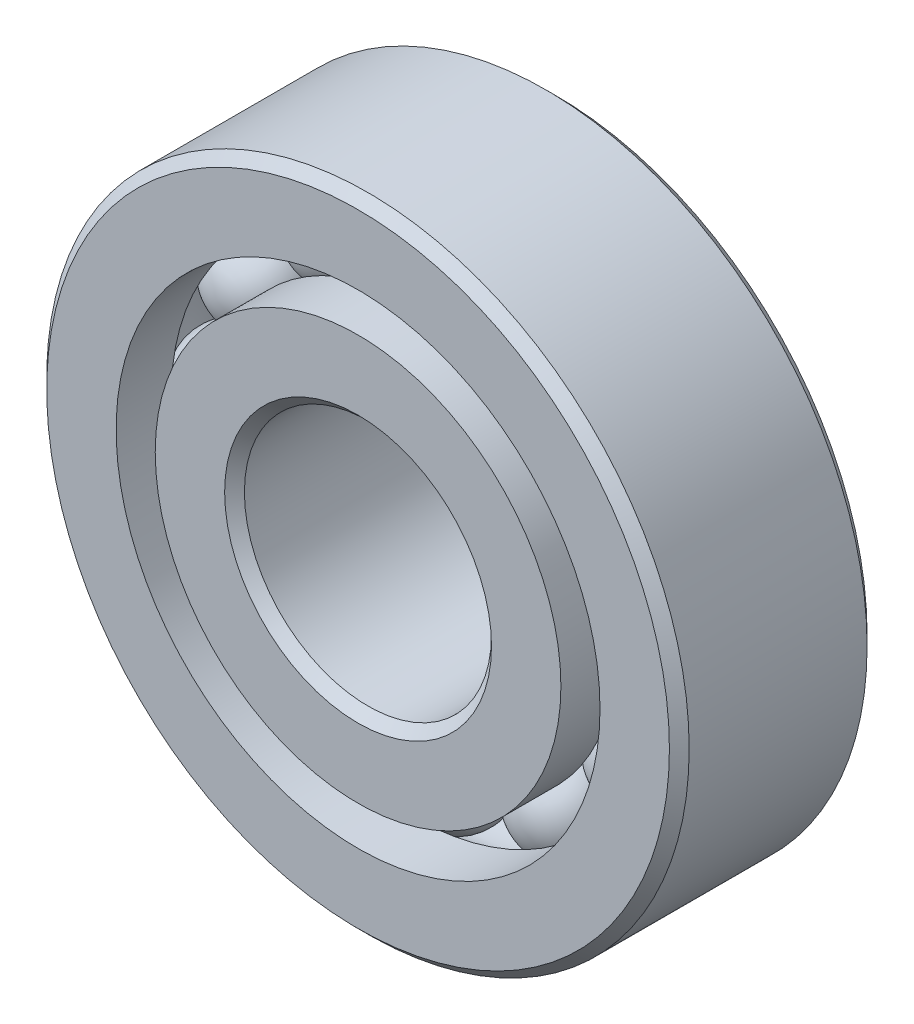
SolidWorks part; units mm, degrees
ref_plane "Front Plane" through (0, 0, 0) normal (0, 0, 1) x (1, 0, 0)
ref_plane "Top Plane" through (0, 0, 0) normal (0, 1, 0) x (1, 0, 0)
ref_plane "Right Plane" through (0, 0, 0) normal (1, 0, 0) x (0, 0, -1)
sketch "Sketch1" plane through (0, 0, 0) normal (1, 0, 0) x (0, 0, -1)
  line L0 (-4, 0) -> (4, 0) construction
  line L1 (0, 13) -> (0, -13) construction
  line L2 (3.6, 13) -> (-3.6, 13)
  line L3 (-3.6, 13) -> (-4, 12.6)
  line L4 (-4, 12.6) -> (-4, 9.7912)
  line L5 (-4, 9.7912) -> (-1.7778, 9.7912)
  line L6 (4, 9.7912) -> (1.7778, 9.7912)
  line L7 (4, 12.6) -> (4, 9.7912)
  line L8 (3.6, 13) -> (4, 12.6)
  line L9 (0, 13) -> (0, 9) construction
  line L10 (0, 9) -> (0, 5) construction
  arc A0 (-1.7778, 9.7912) -> (1.7778, 9.7912) centre (0, 9) cw
  point P14 (0, 5)
  dimension "Width" = 8
  dimension "OD" = 26
  dimension "D1" = 45
  dimension "D2" = 0.4
  dimension "Shaft Dia" = 10
  dimension "D3" = 3.5556
  dimension "D4" = 0.7912
revolve "Revolve1" add sketch "Sketch1" angle 360 about L0
sketch "Sketch3" plane through (0, 0, 0) normal (1, 0, 0) x (0, 0, -1)
  line L0 (-4, 8.2088) -> (-1.7778, 8.2088)
  line L1 (0, 13) -> (0, -13) construction
  line L2 (-4, 12.6) -> (-4, 9.7912) construction
  line L3 (-4, 8.2088) -> (-4, 5.4)
  line L4 (-3.6, 13) -> (-4, 12.6) construction
  line L5 (-4, 5.4) -> (-3.6, 5)
  line L6 (-3.6, 5) -> (3.6, 5)
  line L7 (3.6, 13) -> (3.6, -13) construction
  line L8 (3.6, 5) -> (4, 5.4)
  line L9 (4, -12.6) -> (4, 12.6) construction
  line L10 (4, 5.4) -> (4, 8.2088)
  line L11 (4, 8.2088) -> (1.7778, 8.2088)
  line L13 (3.6, 13) -> (4, 12.6) construction
  arc A0 (1.7778, 9.7912) -> (-1.7778, 9.7912) centre (0, 9) ccw construction
  arc A1 (1.7778, 8.2088) -> (-1.7778, 8.2088) centre (0, 9) cw
revolve "Revolve3" add sketch "Sketch3" angle 360 about L0
sketch "Sketch4" plane through (0, 0, 0) normal (1, 0, 0) x (0, 0, -1)
  line L0 (-1.9459, 9) -> (1.9459, 9)
  arc A2 (-1.9459, 9) -> (1.9459, 9) centre (0, 9) cw
  arc A3 (1.7778, 9.7912) -> (-1.7778, 9.7912) centre (0, 9) ccw construction
revolve "Revolve4" add sketch "Sketch4" angle 360 about L0
ref_axis "Axis1" through (0, 0, -4) along (0, 0, 1)
pattern_circular "CirPattern1" count 12 every 30 about axis through (0, 0, -4) along (0, 0, 1) of bodies 104
sketch "Sketch5" plane through (0, 0, 0) normal (1, 0, 0) x (0, 0, -1)
  line L0 (-4, 9.7912) -> (-1.7778, 9.7912) construction
  line L1 (-3.8, 9.7912) -> (-1.9459, 9.7912)
  line L2 (-3.8, 9.7912) -> (-3.8, 8.2088)
  line L3 (-3.8, 8.2088) -> (-1.9459, 8.2088)
  line L4 (-1.9459, 9.7912) -> (-1.9459, 8.2088)
  line L5 (-4, 8.2088) -> (-1.7778, 8.2088) construction
  line L6 (4, 9.7912) -> (1.7778, 9.7912) construction
  line L7 (3.8, 9.7912) -> (1.9459, 9.7912)
  line L8 (3.8, 9.7912) -> (3.8, 8.2088)
  line L9 (3.8, 8.2088) -> (1.9459, 8.2088)
  line L10 (1.9459, 9.7912) -> (1.9459, 8.2088)
  line L11 (4, 8.2088) -> (1.7778, 8.2088) construction
  line L12 (-3.6, 13) -> (-4, 12.6) construction
  point P18 (-3.8, 12.8)
revolve "Revolve5" [suppressed] add sketch "Sketch5" angle 360 about L0
equation "\"D2@Sketch1\" = \"Width@Sketch1\"*.05"
equation "\"D3@Sketch1\" = \"Width@Sketch1\"/2.25"
equation "\"D4@Sketch1\" = (((\"OD@Sketch1\"-\"Width@Sketch1\")/2)/3.25)/3.5"
equation "\"D2@CirPattern1\" = 360/\"Balls@CirPattern1\""
